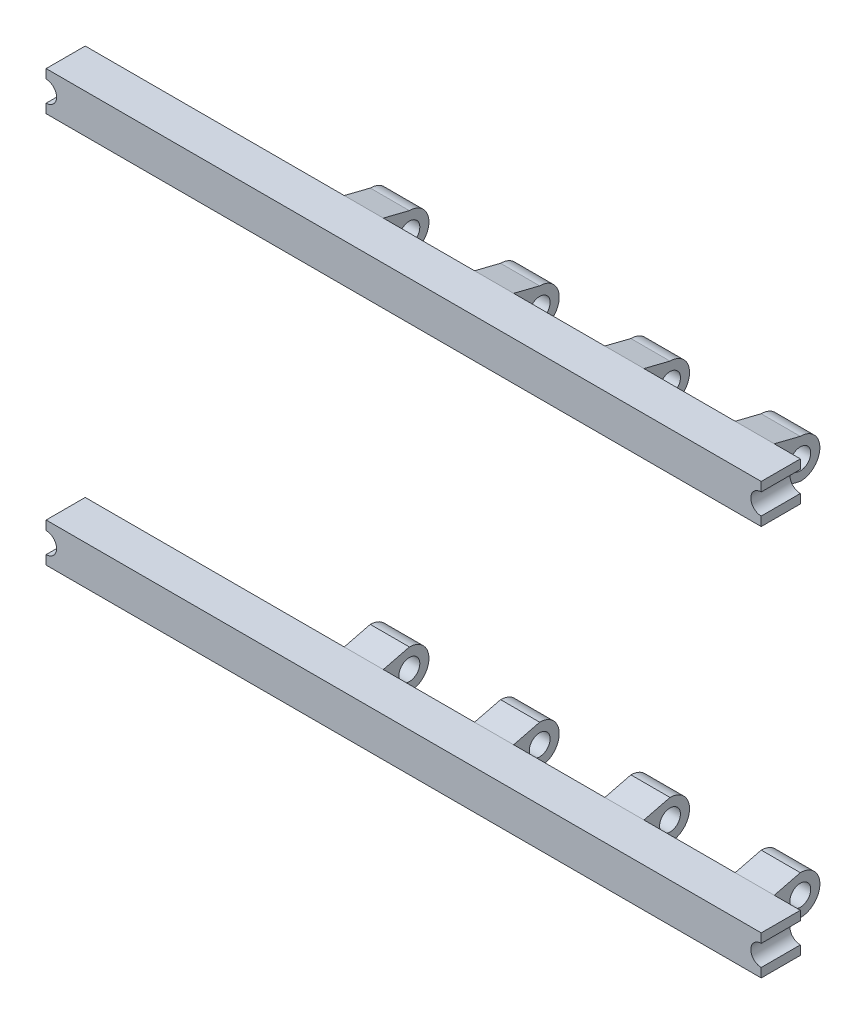
SolidWorks part; units mm, degrees
ref_plane "Front Plane" through (0, 0, 0) normal (0, 0, 1) x (1, 0, 0)
ref_plane "Top Plane" through (0, 0, 0) normal (0, 1, 0) x (1, 0, 0)
ref_plane "Right Plane" through (0, 0, 0) normal (1, 0, 0) x (0, 0, -1)
sketch "Sketch1" plane through (0, 0, 0) normal (0, 0, 1) x (1, 0, 0)
  line L1 (3, -220) -> (112.75, -220)
  line L2 (3, -220) -> (3, -214)
  line L3 (3, -214) -> (112.75, -214)
  line L4 (112.75, -220) -> (112.75, -214)
  line L6 (3, -214) -> (112.75, -220) construction
  line L7 (57.875, -217) -> (57.875, -159) construction
  line L8 (3, -159) -> (112.75, -159) construction
  line L10 (3, -154) -> (112.75, -154)
  line L11 (3, -154) -> (3, -160)
  line L12 (3, -160) -> (112.75, -160)
  line L13 (112.75, -154) -> (112.75, -160)
  point P12 (57.875, -159)
  dimension "D1" = 58
extrude "Boss-Extrude1" add sketch "Sketch1" against normal blind 6 contours L12 L13 L10 L11 | L1 L4 L3 L2
sketch "Sketch2" plane through (112.75, 0, 0) normal (1, 0, 0) x (0, 0, -1)
  line L0 (6, -214) -> (10, -213)
  line L1 (6, -220) -> (10, -219)
  line L2 (6, -220) -> (6, -214)
  line L3 (6, -214) -> (6, -160) construction
  line L4 (6, -187) -> (28.8077, -187) construction
  line L5 (6, -154) -> (6, -160)
  line L6 (6, -154) -> (10, -155)
  line L7 (6, -160) -> (10, -161)
  circle A0 centre (10, -216) radius 1.6
  arc A1 (8.5882, -160.6471) -> (10, -161) centre (10, -158) cw
  arc A2 (8.5882, -213.3529) -> (10, -213) centre (10, -216) ccw
  circle A3 centre (10, -158) radius 1.6
  line M9 (6, -160) -> (6, -154)
  dimension "D1" = 3.2
  dimension "D2" = 6
  dimension "D3" = 58
  dimension "D4" = 4
extrude "Boss-Extrude2" add sketch "Sketch2" against normal blind 6 from offset 4 contours L0 A2 A0 | A2 L0 L2 L1 | A1 L7 A3 | L7 A1 L6 M9 region at (112.75, -217.181, -6.9787) region at (112.75, -213.2588, -9.3147) region at (112.75, -156.819, -6.9787) region at (112.75, -158, -12.9151) offset against normal yes
pattern_linear "LPattern1" count 4 spacing 20 along (-1, 0, 0) of "Boss-Extrude2"
sketch "Sketch3" plane through (0, 0, 0) normal (0, 0, 1) x (1, 0, 0)
  line L0 (3, -220) -> (3, -214) construction
  line L1 (3, -154) -> (3, -160) construction
  line L2 (112.75, -154) -> (112.75, -160) construction
  line L4 (112.75, -220) -> (112.75, -214) construction
  circle A0 centre (3, -217) radius 1.6
  circle A1 centre (3, -157) radius 1.6
  circle A2 centre (112.75, -157) radius 1.6
  circle A3 centre (112.75, -217) radius 1.6
  dimension "D1" = 3.2
extrude "Cut-Extrude1" cut sketch "Sketch3" against normal up to next
